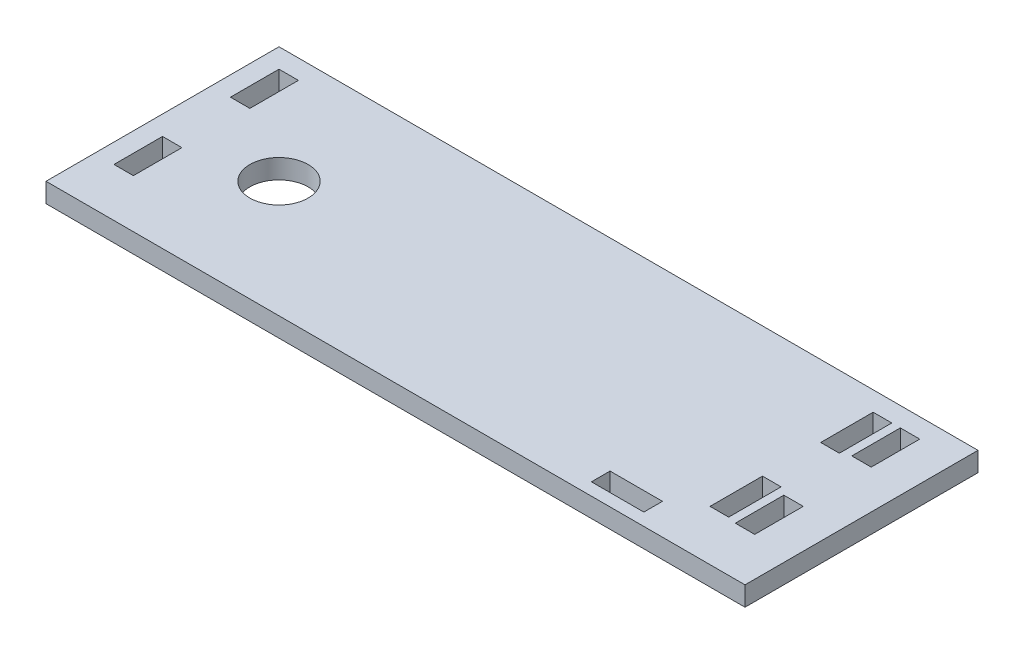
SolidWorks part; units mm, degrees
ref_plane "Front Plane" through (0, 0, 0) normal (0, 0, 1) x (1, 0, 0)
ref_plane "Top Plane" through (0, 0, 0) normal (0, 1, 0) x (1, 0, 0)
ref_plane "Right Plane" through (0, 0, 0) normal (1, 0, 0) x (0, 0, -1)
sketch "Sketch1" plane through (0, 0, 0) normal (0, 1, 0) x (1, 0, 0)
  line L0 (-107.95, -6.35) -> (-101.6, -6.35)
  line L1 (-114.3, 38.1) -> (114.3, 38.1)
  line L2 (-114.3, 38.1) -> (-114.3, -38.1)
  line L3 (-114.3, -38.1) -> (114.3, -38.1)
  line L4 (114.3, 38.1) -> (114.3, -38.1)
  line L5 (-107.95, 31.75) -> (-101.6, 31.75)
  line L6 (-107.95, 31.75) -> (-107.95, 15.875)
  line L7 (-107.95, 15.875) -> (-101.6, 15.875)
  line L8 (-101.6, 31.75) -> (-101.6, 15.875)
  line L9 (-107.95, -6.35) -> (-107.95, -22.225)
  line L10 (-107.95, -22.225) -> (-101.6, -22.225)
  line L11 (-101.6, -6.35) -> (-101.6, -22.225)
  line L12 (86.36, -4.445) -> (86.36, -21.59)
  line L13 (95.25, 31.75) -> (101.6, 31.75)
  line L14 (95.25, 31.75) -> (95.25, 15.875)
  line L15 (95.25, 15.875) -> (101.6, 15.875)
  line L16 (101.6, 31.75) -> (101.6, 15.875)
  line L17 (95.25, -6.35) -> (101.6, -6.35)
  line L18 (95.25, -6.35) -> (95.25, -22.225)
  line L19 (95.25, -22.225) -> (101.6, -22.225)
  line L20 (101.6, -6.35) -> (101.6, -22.225)
  line L21 (86.36, 31.75) -> (92.456, 31.75)
  line L22 (86.36, 31.75) -> (86.36, 14.605)
  line L23 (86.36, 14.605) -> (92.456, 14.605)
  line L24 (92.456, 31.75) -> (92.456, 14.605)
  line L25 (86.36, -4.445) -> (92.456, -4.445)
  line L26 (92.456, -4.445) -> (92.456, -21.59)
  line L27 (86.36, -21.59) -> (92.456, -21.59)
  line L28 (86.36, 31.75) -> (86.36, -4.445) construction
  line L30 (60.0075, -27.94) -> (77.1525, -27.94)
  line L31 (60.0075, -27.94) -> (60.0075, -34.036)
  line L32 (60.0075, -34.036) -> (77.1525, -34.036)
  line L33 (77.1525, -27.94) -> (77.1525, -34.036)
  circle A0 centre (-76.2, 0) radius 9.525
  point P7 (-114.3, 0)
  point P13 (0, 38.1)
  point P39 (77.1525, -30.988)
  dimension "D1" = 19.05
  dimension "D2" = 6.35
  dimension "D3" = 38.1
  dimension "D4" = 190.5
  dimension "D5" = 6.35
  dimension "D6" = 15.875
  dimension "D7" = 6.35
  dimension "D8" = 38.1
  dimension "D9" = 22.225
  dimension "D10" = 196.85
  dimension "D11" = 6.096
  dimension "D12" = 17.145
  dimension "D13" = 162.56
  dimension "D14" = 6.35
  dimension "D16" = 36.195
  dimension "D17" = 6.096
  dimension "D18" = 17.145
  dimension "D19" = 9.2075
  dimension "D20" = 6.35
  dimension "D15" = 2
extrude "Boss-Extrude1" add sketch "Sketch1" along normal blind 6.35
